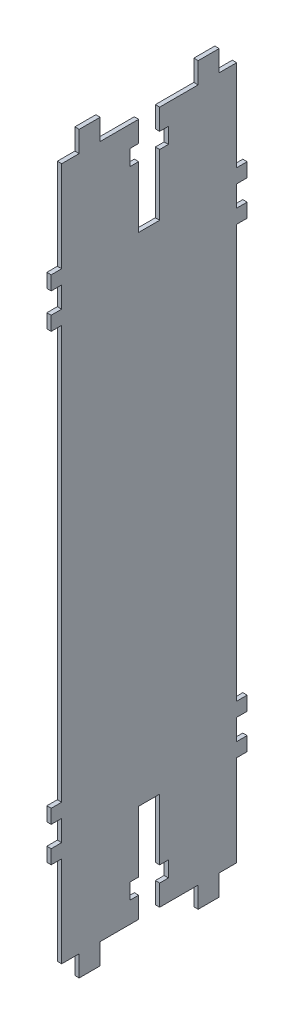
SolidWorks part; units mm, degrees
ref_plane "Front Plane" through (0, 0, 0) normal (0, 0, 1) x (1, 0, 0)
ref_plane "Top Plane" through (0, 0, 0) normal (0, 1, 0) x (1, 0, 0)
ref_plane "Right Plane" through (0, 0, 0) normal (1, 0, 0) x (0, 0, -1)
sketch "Sketch1" plane through (0, 0, 0) normal (1, 0, 0) x (0, 0, -1)
  line L0 (-60.5005, -152.4629) -> (-60.5005, -166.9829)
  line L1 (-67.7605, -152.4629) -> (-60.5005, -152.4629)
  line L2 (-67.7605, -142.7835) -> (-67.7605, -152.4629)
  line L3 (-60.5005, -142.7835) -> (-67.7605, -142.7835)
  line L4 (-60.5005, 142.78) -> (-60.5005, -142.7835)
  line L5 (-67.7605, 142.78) -> (-60.5005, 142.78)
  line L6 (-67.7605, 152.4613) -> (-67.7605, 142.78)
  line L7 (-60.5005, 152.4613) -> (-67.7605, 152.4613)
  line L8 (-60.5005, 166.9812) -> (-60.5005, 152.4613)
  line L9 (-67.7605, 166.9812) -> (-60.5005, 166.9812)
  line L10 (-67.7605, 176.6623) -> (-67.7605, 166.9812)
  line L11 (-60.5005, 176.6623) -> (-67.7605, 176.6623)
  line L12 (-60.5005, 239.5797) -> (-60.5005, 176.6623)
  line L13 (-48.3998, 239.5797) -> (-60.5005, 239.5797)
  line L14 (-48.3998, 254.1015) -> (-48.3998, 239.5797)
  line L15 (-33.8815, 254.1015) -> (-48.3998, 254.1015)
  line L16 (-33.8815, 239.5797) -> (-33.8815, 254.1015)
  line L17 (-7.2693, 239.5797) -> (-33.8815, 239.5797)
  line L18 (-7.2693, 225.0631) -> (-7.2693, 239.5797)
  line L19 (-13.3169, 225.0631) -> (-7.2693, 225.0631)
  line L20 (-13.3169, 214.2148) -> (-13.3169, 225.0631)
  line L21 (-7.2693, 214.2148) -> (-13.3169, 214.2148)
  line L22 (-7.2693, 171.8218) -> (-7.2693, 214.2148)
  line L23 (7.2525, 171.8218) -> (-7.2693, 171.8218)
  line L24 (7.2525, 214.2148) -> (7.2525, 171.8218)
  line L25 (13.3102, 214.2148) -> (7.2525, 214.2148)
  line L26 (13.3102, 225.0631) -> (13.3102, 214.2148)
  line L27 (7.2525, 225.0631) -> (13.3102, 225.0631)
  line L28 (7.2525, 239.5797) -> (7.2525, 225.0631)
  line L29 (33.8798, 239.5797) -> (7.2525, 239.5797)
  line L30 (33.8798, 254.1015) -> (33.8798, 239.5797)
  line L31 (48.4014, 254.1015) -> (33.8798, 254.1015)
  line L32 (48.4014, 239.5797) -> (48.4014, 254.1015)
  line L33 (60.5005, 239.5797) -> (48.4014, 239.5797)
  line L34 (60.5005, 176.6623) -> (60.5005, 239.5797)
  line L35 (67.7604, 176.6623) -> (60.5005, 176.6623)
  line L36 (67.7604, 166.9812) -> (67.7604, 176.6623)
  line L37 (60.5005, 166.9812) -> (67.7604, 166.9812)
  line L38 (60.5005, 152.4613) -> (60.5005, 166.9812)
  line L39 (67.7604, 152.4613) -> (60.5005, 152.4613)
  line L40 (67.7604, 142.78) -> (67.7604, 152.4613)
  line L41 (60.5005, 142.78) -> (67.7604, 142.78)
  line L42 (60.5005, -142.7835) -> (60.5005, 142.78)
  line L43 (67.7604, -142.7835) -> (60.5005, -142.7835)
  line L44 (67.7604, -152.4629) -> (67.7604, -142.7835)
  line L45 (60.5005, -152.4629) -> (67.7604, -152.4629)
  line L46 (60.5005, -166.9829) -> (60.5005, -152.4629)
  line L47 (67.7604, -166.9829) -> (60.5005, -166.9829)
  line L48 (67.7604, -176.6624) -> (67.7604, -166.9829)
  line L49 (60.5005, -176.6624) -> (67.7604, -176.6624)
  line L50 (60.5005, -239.5814) -> (60.5005, -176.6624)
  line L51 (48.4014, -239.5814) -> (60.5005, -239.5814)
  line L52 (48.4014, -254.1014) -> (48.4014, -239.5814)
  line L53 (33.8798, -254.1014) -> (48.4014, -254.1014)
  line L54 (33.8798, -239.5814) -> (33.8798, -254.1014)
  line L55 (7.2525, -239.5814) -> (33.8798, -239.5814)
  line L56 (7.2525, -225.0631) -> (7.2525, -239.5814)
  line L57 (13.3102, -225.0631) -> (7.2525, -225.0631)
  line L58 (13.3102, -214.2031) -> (13.3102, -225.0631)
  line L59 (7.2525, -214.2031) -> (13.3102, -214.2031)
  line L60 (7.2525, -171.8219) -> (7.2525, -214.2031)
  line L61 (-7.2693, -171.8219) -> (7.2525, -171.8219)
  line L62 (-7.2693, -214.2031) -> (-7.2693, -171.8219)
  line L63 (-13.3169, -214.2031) -> (-7.2693, -214.2031)
  line L64 (-13.3169, -225.0631) -> (-13.3169, -214.2031)
  line L65 (-7.2693, -225.0631) -> (-13.3169, -225.0631)
  line L66 (-7.2693, -239.5814) -> (-7.2693, -225.0631)
  line L67 (-33.8815, -239.5814) -> (-7.2693, -239.5814)
  line L68 (-33.8815, -254.1014) -> (-33.8815, -239.5814)
  line L69 (-48.3998, -254.1014) -> (-33.8815, -254.1014)
  line L70 (-48.3998, -239.5814) -> (-48.3998, -254.1014)
  line L71 (-60.5005, -239.5814) -> (-48.3998, -239.5814)
  line L72 (-60.5005, -176.6624) -> (-60.5005, -239.5814)
  line L73 (-67.7605, -176.6624) -> (-60.5005, -176.6624)
  line L74 (-67.7605, -166.9829) -> (-67.7605, -176.6624)
  line L75 (-60.5005, -166.9829) -> (-67.7605, -166.9829)
extrude "Boss-Extrude1" add sketch "Sketch1" along normal blind 3
